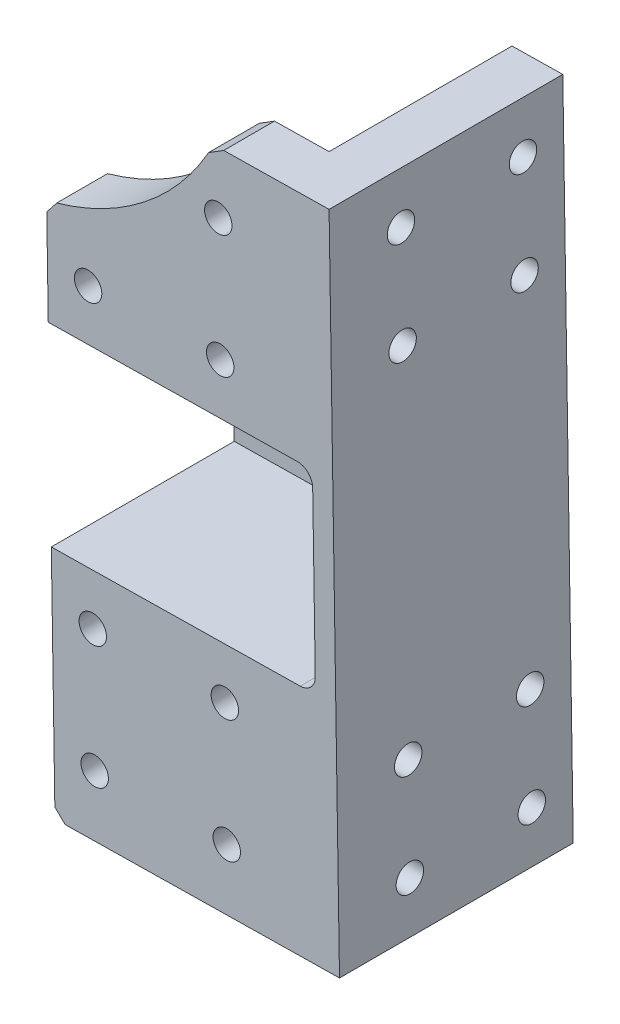
SolidWorks part; units mm, degrees
material "AISI 304"
ref_plane "Front Plane" through (0, 0, 0) normal (0, 0, 1) x (1, 0, 0)
ref_plane "Top Plane" through (0, 0, 0) normal (0, 1, 0) x (1, 0, 0)
ref_plane "Right Plane" through (0, 0, 0) normal (1, 0, 0) x (0, 0, -1)
sketch "Sketch1" plane through (0, 0, 0) normal (0, 0, 1) x (1, 0, 0)
  line L0 (134.2441, -107.3765) -> (135.2702, -172.3684)
  line L1 (135.2702, -172.3684) -> (107.2737, -172.8104)
  line L2 (135.2702, -172.3684) -> (58.3983, -173.582) construction
  line L3 (107.2737, -172.8104) -> (106.4478, -120.4953)
  line L4 (106.9264, -150.8131) -> (107.2421, -170.8106) construction
  line L5 (134.2441, -107.3765) -> (122.8737, -107.556)
  line L7 (106.2792, -109.8182) -> (106.5949, -129.8157) construction
  line L8 (108.2474, -107.7869) -> (131.2445, -107.4238) construction
  line L9 (110.7207, -137.7505) -> (110.8628, -146.7505) construction
  line L10 (128.6553, -133.4663) -> (128.8605, -146.4663) construction
  line L11 (110.8628, -146.7505) -> (128.8605, -146.4663) construction
  line L13 (104.9545, -152.8445) -> (134.9545, -152.3709) construction
  circle A1 centre (110.7207, -137.7505) radius 1.35
  arc A2 (122.8737, -107.556) -> (106.4478, -120.4953) centre (100.6084, -96.1868) cw
  arc A3 (75.6968, -121.8977) -> (125.5201, -70.4759) centre (100.6084, -96.1868) ccw construction
  circle A4 centre (111.1785, -166.748) radius 1.35
  circle A5 centre (124.1769, -166.5428) radius 1.35
  circle A6 centre (123.9875, -154.5443) radius 1.35
  circle A7 centre (110.9891, -154.7495) radius 1.35
  circle A8 centre (123.5297, -125.5479) radius 1.35
  circle A9 centre (110.5313, -125.7531) radius 1.35
  circle A10 centre (123.3402, -113.5494) radius 1.35
  circle A11 centre (128.6553, -133.4663) radius 1.35
  circle A12 centre (110.8628, -146.7505) radius 1.35
  circle A13 centre (128.8605, -146.4663) radius 1.35
  dimension "D1" = 25
  dimension "D2" = 2.7
  dimension "D7" = 2.7
  dimension "D3" = 4
  dimension "D4" = 6
  dimension "D5" = 9
  dimension "D6" = 6
  dimension "D8" = 13
extrude "Extrude1" add sketch "Sketch1" along normal blind 23
sketch "Sketch2" plane through (132.5158, 2.0922, 0) normal (0.9999, 0.0158, 0) x (0, 0, -1)
  line L0 (-23, -109.4823) -> (-23, -174.4823) construction
  line L1 (-16, -114.4823) -> (-4, -114.4823) construction
  line L2 (-16, -114.4823) -> (-16, -169.4823) construction
  line L3 (-16, -169.4823) -> (-4, -169.4823) construction
  line L4 (-4, -114.4823) -> (-4, -169.4823) construction
  line L5 (0, -174.4823) -> (0, -109.4823) construction
  line L6 (-23, -109.4823) -> (0, -109.4823) construction
  line L7 (-23, -174.4823) -> (0, -174.4823) construction
  circle A0 centre (-16, -114.4823) radius 1.35
  circle A1 centre (-4, -114.4823) radius 1.35
  circle A2 centre (-16, -124.4823) radius 1.35
  circle A3 centre (-4, -124.4823) radius 1.35
  circle A4 centre (-16, -169.4823) radius 1.35
  circle A5 centre (-4, -169.4823) radius 1.35
  circle A6 centre (-16, -159.4823) radius 1.35
  circle A7 centre (-4, -159.4823) radius 1.35
  dimension "D5" = 2.7
  dimension "D6" = 10
  dimension "D7" = 10
  dimension "D8" = 10
  dimension "D9" = 10
  dimension "D1" = 7
  dimension "D2" = 4
  dimension "D3" = 5
  dimension "D4" = 5
extrude "Cut-Extrude1" cut sketch "Sketch2" against normal blind 10
chamfer "Chamfer3" distance 1 3 edges at (122.8737, -107.556, 11.5) (106.4478, -120.4953, 11.5) (107.2737, -172.8104, 11.5)
sketch "Sketch3" plane through (0, 0, 23) normal (0, 0, 1) x (1, 0, 0)
  line L0 (104.0115, -130.855) -> (131.1076, -130.4272)
  line L1 (102.5354, -132.3785) -> (102.788, -148.3781)
  line L2 (132.6311, -131.9034) -> (132.8837, -147.903)
  line L3 (104.3115, -149.8543) -> (131.4076, -149.4265)
  line L4 (135.2702, -172.3684) -> (134.2441, -107.3765) construction
  circle A1 centre (128.6553, -133.4663) radius 1.35 construction
  circle A2 centre (128.8605, -146.4663) radius 1.35 construction
  arc A3 (102.788, -148.3781) -> (104.3115, -149.8543) centre (104.2878, -148.3545) ccw
  arc A4 (132.8837, -147.903) -> (131.4076, -149.4265) centre (131.3839, -147.9267) cw
  arc A5 (131.1076, -130.4272) -> (132.6311, -131.9034) centre (131.1313, -131.927) cw
  arc A6 (102.5354, -132.3785) -> (104.0115, -130.855) centre (104.0352, -132.3548) cw
  dimension "D5" = 1.5
  dimension "D2" = 2
  dimension "D3" = 3
  dimension "D4" = 3
extrude "Extrude2" cut sketch "Sketch3" against normal blind 18
sketch "Sketch4" plane through (0, 0, 0) normal (0, 0, -1) x (-1, 0, 0)
  line L0 (-128.9953, -91.6545) -> (-129.5526, -126.953)
  line L1 (-127.4718, -90.1784) -> (-94.8979, -90.6927)
  line L2 (-128.0765, -128.4765) -> (-95.5026, -128.9907)
  line L3 (-93.4218, -92.2162) -> (-93.9791, -127.5146)
  line L4 (-129.963, -152.9497) -> (-130.4391, -183.1041)
  line L5 (-128.4395, -151.4736) -> (-101.1585, -151.9043)
  line L6 (-128.963, -184.6276) -> (-101.682, -185.0583)
  line L7 (-99.6824, -153.4278) -> (-100.1585, -183.5821)
  line L8 (-135.2702, -172.3684) -> (-134.2441, -107.3765) construction
  circle A0 centre (-123.9875, -154.5443) radius 1.35 construction
  circle A3 centre (-123.5297, -125.5479) radius 1.35 construction
  arc A4 (-101.682, -185.0583) -> (-100.1585, -183.5821) centre (-101.6583, -183.5585) ccw
  arc A5 (-130.4391, -183.1041) -> (-128.963, -184.6276) centre (-128.9393, -183.1277) ccw
  arc A6 (-128.4395, -151.4736) -> (-129.963, -152.9497) centre (-128.4632, -152.9734) ccw
  arc A7 (-101.1585, -151.9043) -> (-99.6824, -153.4278) centre (-101.1822, -153.4041) cw
  arc A8 (-95.5026, -128.9907) -> (-93.9791, -127.5146) centre (-95.4789, -127.4909) ccw
  arc A9 (-129.5526, -126.953) -> (-128.0765, -128.4765) centre (-128.0528, -126.9766) ccw
  arc A10 (-94.8979, -90.6927) -> (-93.4218, -92.2162) centre (-94.9216, -92.1925) cw
  arc A11 (-127.4718, -90.1784) -> (-128.9953, -91.6545) centre (-127.4955, -91.6782) ccw
  dimension "D9" = 1.5
  dimension "D1" = 5
  dimension "D2" = 5
  dimension "D3" = 3
  dimension "D6" = 3
extrude "Extrude3" cut sketch "Sketch4" against normal blind 18
